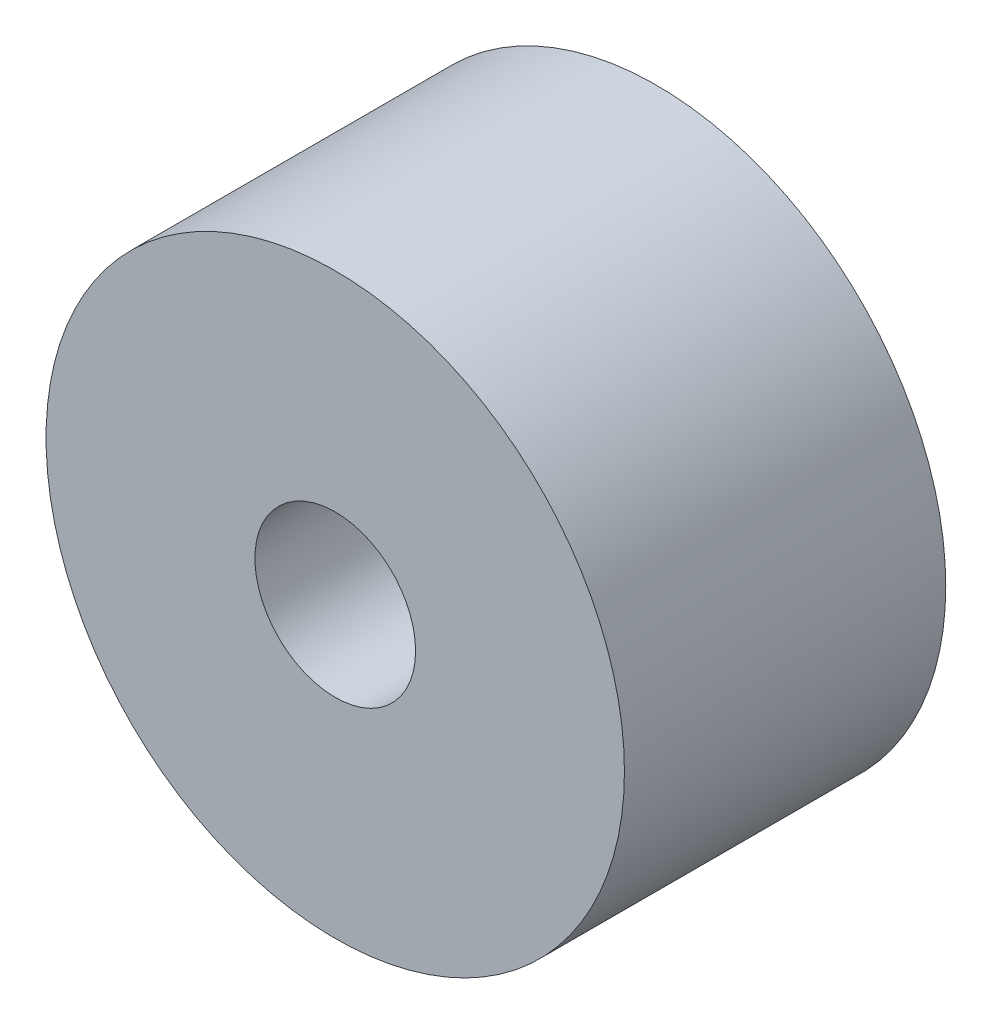
SolidWorks part; units mm, degrees
ref_plane "前视基准面" through (0, 0, 0) normal (0, 0, 1) x (1, 0, 0)
ref_plane "上视基准面" through (0, 0, 0) normal (0, 1, 0) x (1, 0, 0)
ref_plane "右视基准面" through (0, 0, 0) normal (1, 0, 0) x (0, 0, -1)
other "Configuration Table"
sketch "Sketch1" plane through (0, 0, 0) normal (0, 0, 1) x (1, 0, 0)
  circle A0 centre (0, 0) radius 18
extrude "Boss-Extrude1" add sketch "Sketch1" along normal blind 20
sketch "Sketch2" plane through (0, 0, 0) normal (0, 0, 1) x (1, 0, 0)
  circle A0 centre (0, 0) radius 5
extrude "Cut-Extrude1" cut sketch "Sketch2" along normal blind 20
ref_plane "bottom_face" through (0, 0, 0) normal (0, 0, 1) x (1, 0, 0)
sketch3d "3DSketch1"
  line L0 (0, 0, 0) -> (0, 0, 20) construction
ref_axis "center_axis" through (0, 0, 0) along (0, 0, 1)
